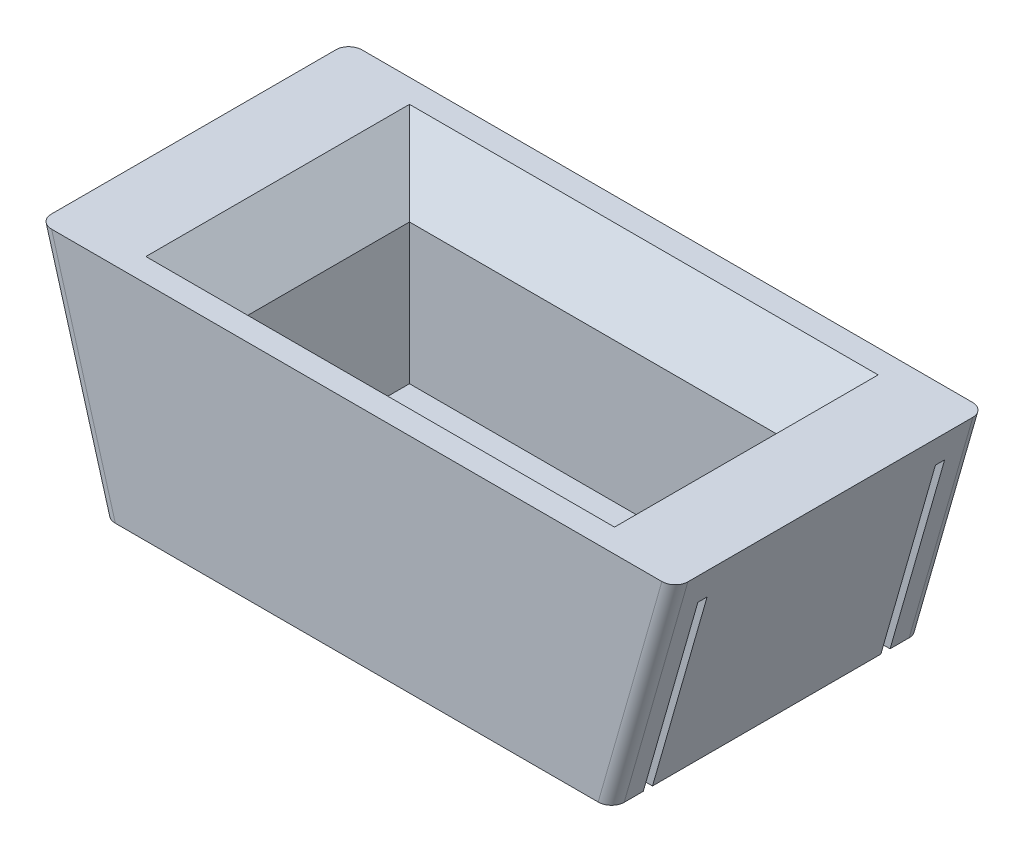
SolidWorks part; units mm, degrees
ref_plane "Front" through (0, 0, 0) normal (0, 0, 1) x (1, 0, 0)
ref_plane "Top" through (0, 0, 0) normal (0, 1, 0) x (1, 0, 0)
ref_plane "Right" through (0, 0, 0) normal (1, 0, 0) x (0, 0, -1)
sketch "Sketch1" plane through (0, 0, 0) normal (0, 1, 0) x (1, 0, 0)
  line L1 (-63.5, -24.6126) -> (63.5, -24.6126)
  line L2 (-63.5, -24.6126) -> (-63.5, 24.6126)
  line L3 (-63.5, 24.6126) -> (63.5, 24.6126)
  line L4 (63.5, -24.6126) -> (63.5, 24.6126)
  line L5 (0, 24.6126) -> (0, -24.6126) construction
  line L6 (-63.5, 0) -> (63.5, 0) construction
  line L7 (-63.5, -22.7711) -> (63.5, -22.7711)
  line L8 (-63.5, -22.7711) -> (-63.5, 22.7711)
  line L9 (-63.5, 22.7711) -> (63.5, 22.7711)
  line L10 (63.5, -22.7711) -> (63.5, 22.7711)
  line L11 (0, 22.7711) -> (0, -22.7711) construction
  line L12 (-63.5, 0) -> (63.5, 0) construction
  line L13 (-63.5, -30.9626) -> (63.5, -30.9626)
  line L14 (-63.5, -30.9626) -> (-63.5, 30.9626)
  line L15 (-63.5, 30.9626) -> (63.5, 30.9626)
  line L16 (63.5, -30.9626) -> (63.5, 30.9626)
  line L17 (0, 30.9626) -> (0, -30.9626) construction
  line L18 (-63.5, 0) -> (63.5, 0) construction
  point P0 (0, 0)
  point P4 (0, 0)
  point P8 (0, 0)
  dimension "D1" = 49.2252
  dimension "D2" = 127
  dimension "D3" = 1.8415
  dimension "D4" = 6.35
extrude "Boss-Extrude1" add sketch "Sketch1" along normal blind 44.45 contours L3 L16 L15 L14 | L13 L16 L1 L14 | L3 L4 L1 L2 region at (0, 0, 27.7876) region at (0, 0, -27.7876)
extrude "Cut-Extrude2" cut sketch "Sketch1<3>" along normal blind 38.1 contours L2 L9 L4 L3 | L7 L2 L1 L4 region at (0, 0, 23.6919) region at (0, 0, -23.6919)
sketch "Sketch1<3>" plane through (0, 0, 0) normal (0, 1, 0) x (1, 0, 0) same geometry as "Sketch1"
sketch "Sketch2" plane through (0, 44.45, 0) normal (0, 1, 0) x (1, 0, 0)
  line L1 (-36.576, -16.129) -> (36.576, -16.129)
  line L2 (-36.576, -16.129) -> (-36.576, 16.129)
  line L3 (-36.576, 16.129) -> (36.576, 16.129)
  line L4 (36.576, -16.129) -> (36.576, 16.129)
  line L5 (0, 16.129) -> (0, -16.129) construction
  line L6 (-36.576, 0) -> (36.576, 0) construction
  line L11 (0, 12.7) -> (0, -12.7) construction
  line L12 (-20.32, 0) -> (20.32, 0) construction
  line L13 (-3.2196, -11.5914) -> (32.2231, -11.5914)
  line L14 (-3.2196, -11.5914) -> (-3.2196, 11.5914)
  line L15 (-3.2196, 11.5914) -> (32.2231, 11.5914)
  line L16 (32.2231, -11.5914) -> (32.2231, 11.5914)
  line L17 (14.5018, 11.5914) -> (14.5018, -11.5914) construction
  line L18 (-3.2196, 0) -> (32.2231, 0) construction
  point P0 (0, 0)
  point P4 (0, 0)
  point P5 (14.5018, 0)
  dimension "D1" = 32.258
  dimension "D2" = 73.152
extrude "Cut-Extrude3" cut sketch "Sketch2" against normal blind 38.1
chamfer "Chamfer2" distance 10.16 angle 45 4 edges at (0, 44.45, 16.129) (-36.576, 44.45, 0) (0, 44.45, -16.129) (36.576, 44.45, 0)
sketch "Sketch7" plane through (0, 0, 30.9626) normal (0, 0, 1) x (1, 0, 0)
  line L0 (-63.5, 44.45) -> (-63.5, 0)
  line L1 (-63.5, 44.45) -> (63.5, 44.45) construction
  line L2 (-63.5, 44.45) -> (-63.5, 0) construction
  line L3 (-63.5, 0) -> (63.5, 0) construction
  line L4 (63.5, 44.45) -> (63.5, 0) construction
  line L7 (-63.5, 0) -> (-50.7955, 0)
  line L8 (-50.7955, 0) -> (-63.5, 44.45)
  line L9 (0, 0) -> (0, 44.45)
  line L10 (63.5, 0) -> (50.7955, 0)
  line L11 (63.5, 44.45) -> (63.5, 0)
  line L12 (50.7955, 0) -> (63.5, 44.45)
  point P4 (0, 22.225)
  point P12 (0, 22.225)
  line M13 (-63.5, 0) -> (63.5, 0)
  line M18 (63.5, 0) -> (63.5, 44.45)
  line M19 (-63.5, 44.45) -> (-63.5, 0)
extrude "Cut-Extrude5" cut sketch "Sketch7" against normal through all contours L8 M13 M19 | L12 M13 M18 region at (-59.2652, 14.8167, 30.9626) region at (59.2652, 14.8167, 30.9626)
fillet "Fillet3" radius 2.54 4 edges at (-57.1477, 22.225, 30.9626) (-57.1477, 22.225, -30.9626) (57.1477, 22.225, -30.9626) (57.1477, 22.225, 30.9626)
extrude "Cut-Extrude6" cut sketch "Sketch2<3>" against normal through all contours L15 L16 L13 L14
sketch "Sketch2<3>" plane through (0, 44.45, 0) normal (0, 1, 0) x (1, 0, 0) same geometry as "Sketch2"
chamfer "Chamfer3" distance 2.54 angle 45 4 edges at (14.5018, 0, 11.5914) (-3.2196, 0, 0) (32.2231, 0, 0) (14.5018, 0, -11.5914)
